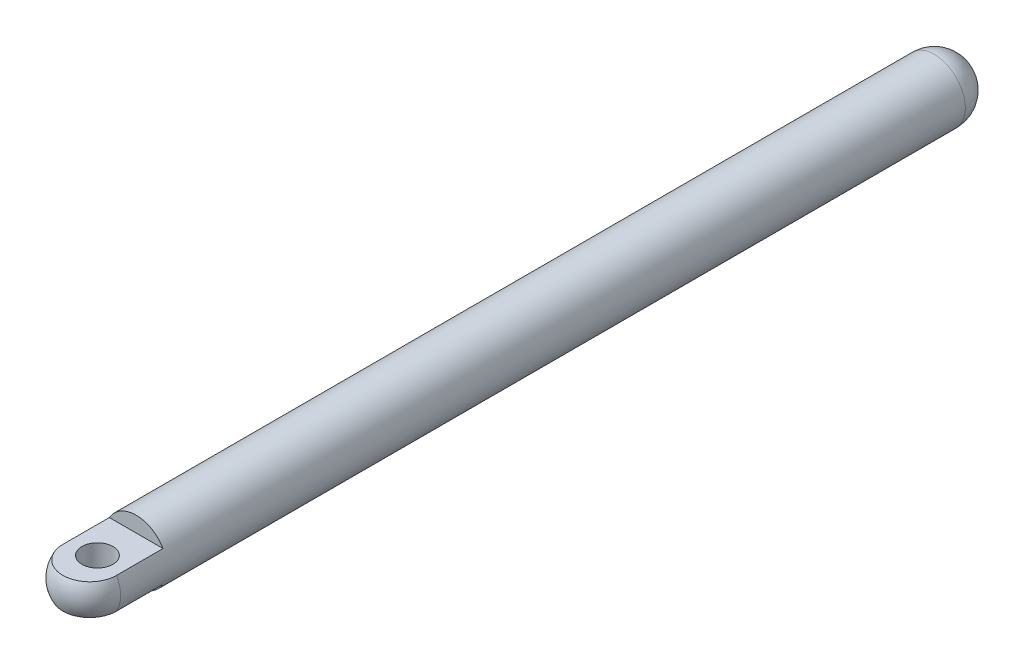
SolidWorks part; units mm, degrees
ref_plane "Płaszczyzna przednia" through (0, 0, 0) normal (0, 0, 1) x (1, 0, 0)
ref_plane "Płaszczyzna górna" through (0, 0, 0) normal (0, 1, 0) x (1, 0, 0)
ref_plane "Płaszczyzna prawa" through (0, 0, 0) normal (1, 0, 0) x (0, 0, -1)
sketch "Szkic1" plane through (0, 0, 0) normal (0, 0, 1) x (1, 0, 0)
  circle A0 centre (0, 0) radius 4
extrude "Dodanie-wyciągnięcie1" add sketch "Szkic1" along normal blind 110
sketch "Szkic2" plane through (0, 0, 0) normal (0, 1, 0) x (1, 0, 0)
  line L0 (-4, -4) -> (-4, -110) construction
  line L1 (-4, -100) -> (4, -100)
  line L2 (-4, -100) -> (-4, -110)
  line L3 (-4, -110) -> (4, -110)
  line L4 (4, -100) -> (4, -110)
fillet "Zaokrąglenie6" radius 4 1 edges at (4, 0, 110)
extrude "Wytnij-wyciągnięcie4" cut sketch "Szkic2" against normal blind 2 from offset 2 offset against normal yes
sketch "Szkic5" plane through (0, -2, 0) normal (0, -1, 0) x (1, 0, 0)
  line L1 (-3.4641, 100) -> (3.4641, 100)
  line L2 (-3.4641, 100) -> (-3.4641, 110)
  line L3 (-3.4641, 110) -> (3.4641, 110)
  line L4 (3.4641, 100) -> (3.4641, 110)
extrude "Wytnij-wyciągnięcie5" cut sketch "Szkic5" against normal blind 2 from offset 4 offset against normal yes
sketch "Szkic6" plane through (0, -2, 0) normal (0, -1, 0) x (1, 0, 0)
  circle A0 centre (0, 105) radius 2
extrude "Wytnij-wyciągnięcie6" cut sketch "Szkic6" against normal up to next
sketch "Szkic8" plane through (0, 0, 0) normal (0, 0, -1) x (-1, 0, 0)
  circle A0 centre (0, 0) radius 4
extrude "Dodanie-wyciągnięcie2" add sketch "Szkic8" along normal blind 7
fillet "Zaokrąglenie7" radius 4 1 edges at (-4, 0, -7)
